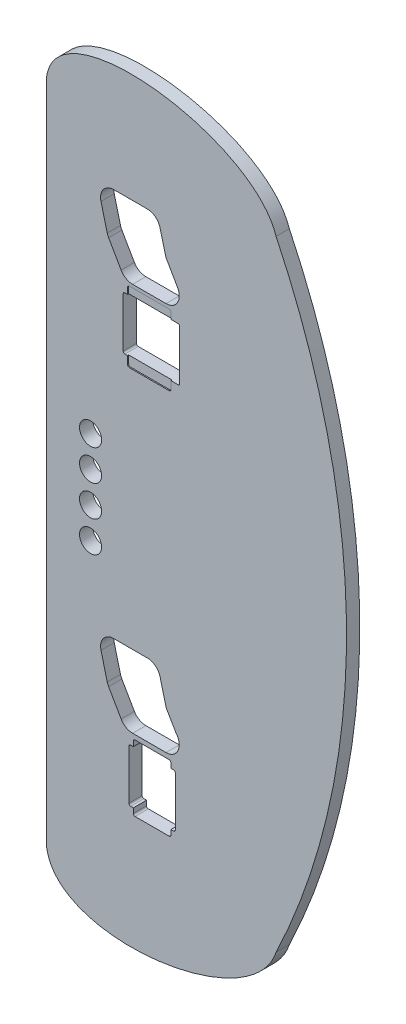
SolidWorks part; units mm, degrees
material "Pine"
ref_plane "Front Plane" through (0, 0, 0) normal (0, 0, 1) x (1, 0, 0)
ref_plane "Top Plane" through (0, 0, 0) normal (0, 1, 0) x (1, 0, 0)
ref_plane "Right Plane" through (0, 0, 0) normal (1, 0, 0) x (0, 0, -1)
sketch "Sketch1" plane through (0, 0, 0) normal (0, 1, 0) x (1, 0, 0)
  line L0 (-92.9216, 89.0184) -> (669.0784, 89.0184)
  line L1 (669.0784, 89.0184) -> (669.0784, 419.2184)
  line L2 (-92.9216, 89.0184) -> (-92.9216, 419.2184)
  line L5 (110.2784, 495.4184) -> (465.8784, 495.4184)
  line L8 (110.2784, 495.4184) -> (-92.9216, 419.2184)
  line L9 (465.8784, 495.4184) -> (669.0784, 419.2184)
  line L10 (-92.9216, 495.4184) -> (669.0784, 495.4184) construction
sketch "Sketch2" plane through (0, 0, 0) normal (0, 0, 1) x (1, 0, 0)
  line L95 (1361.0966, 1819.7347) -> (1361.0966, 996.3635)
  arc A0 (1691.2966, 1027.0491) -> (1691.2966, 1789.0491) centre (733.0004, 1408.0491) ccw
  spline S0 degree 3 poles (1691.2966, 1027.0491) (1656.7077, 922.0591) (1371.3251, 886.2968) (1361.0966, 996.3635) knots 0 0 0 0 7.629784 7.629784 7.629784 7.629784
  spline S1 degree 3 poles (1691.2966, 1789.0491) (1656.7629, 1894.0573) (1371.3251, 1929.8013) (1361.0966, 1819.7347) knots 0 0 0 0 7.638295 7.638295 7.638295 7.638295
sketch "Sketch4" plane through (0, 0, 0) normal (0, 0, 1) x (1, 0, 0)
  line L0 (1439.599, 1277.0692) -> (1448.5991, 1242.0693)
  line L1 (1450.5414, 1237.3053) -> (1468.5414, 1206.0553)
  line L2 (1540.0357, 1097.2035) -> (1540.0357, 1104.1885)
  line L3 (1486.0607, 1185.151) -> (1486.0607, 1006.8697) construction
  line L4 (1486.0607, 1187.3735) -> (1486.0607, 1180.3885)
  line L5 (1540.0357, 1006.8697) -> (1540.0357, 1185.151) construction
  line L6 (1544.7982, 1189.9135) -> (1481.2982, 1189.9135) construction
  line L7 (1488.6007, 1094.6635) -> (1537.4957, 1094.6635)
  line L8 (1482.2507, 1104.1885) -> (1543.8457, 1104.1885)
  line L9 (1546.3857, 1106.7285) -> (1546.3857, 1177.8485)
  line L10 (1543.8457, 1180.3885) -> (1482.2507, 1180.3885)
  line L11 (1479.7107, 1106.7285) -> (1479.7107, 1177.8485)
  line L14 (1550.1957, 1739.1885) -> (1473.9957, 1739.1885)
  line L16 (1471.4557, 1665.5285) -> (1471.4557, 1736.6485)
  line L18 (1473.9957, 1662.9885) -> (1550.1957, 1662.9885)
  line L20 (1540.0357, 1180.3885) -> (1540.0357, 1187.3735)
  line L21 (1486.0607, 1104.1885) -> (1486.0607, 1097.2035)
  line L22 (1540.0357, 1739.1885) -> (1540.0357, 1748.2626)
  line L24 (1485.0488, 1196.5135) -> (1533.0488, 1196.5135)
  line L25 (1550.8991, 1222.2168) -> (1533.383, 1252.007)
  line L26 (1524.4986, 1286.5577) -> (1533.383, 1252.007)
  line L27 (1459.748, 1300.7875) -> (1504.3496, 1300.7875)
  line L28 (1439.599, 1835.8692) -> (1448.5991, 1800.8693)
  line L29 (1450.5414, 1796.1053) -> (1468.5414, 1764.8553)
  line L30 (1485.0488, 1755.3135) -> (1533.0488, 1755.3135)
  line L31 (1549.5562, 1783.8718) -> (1532.852, 1812.8721)
  line L32 (1524.4986, 1845.3577) -> (1532.852, 1812.8721)
  line L33 (1458.0488, 1859.6635) -> (1506.0488, 1859.6635)
  line L34 (1480.3457, 1649.2026) -> (1537.4957, 1649.2026)
  line L35 (1552.7357, 1665.5285) -> (1552.7357, 1736.6485)
  line L36 (1477.8057, 1651.7426) -> (1477.8057, 1662.9885)
  line L37 (1480.3457, 1750.8026) -> (1537.4957, 1750.8026)
  line L38 (1513.0482, 1189.9135) -> (1513.0482, 1196.5135)
  line L39 (1540.0357, 1651.7426) -> (1540.0357, 1748.2626)
  line L40 (1471.4557, 1651.7426) -> (1471.4557, 1748.2626) construction
  line L41 (1477.8057, 1739.1885) -> (1477.8057, 1748.2626)
  line L42 (1477.8057, 1651.7426) -> (1477.8057, 1748.2626) construction
  line L95 (1361.0966, 1948.8635) -> (1361.0966, 996.3635)
  line L115 (1537.4957, 1189.9135) -> (1488.6007, 1189.9135)
  line L202 (1540.0357, 1185.151) -> (1486.0607, 1185.151) construction
  line L203 (1481.2982, 1189.9135) -> (1481.2982, 1006.8697) construction
  line L204 (1544.7982, 1006.8697) -> (1544.7982, 1189.9135) construction
  arc A0 (1691.2966, 1027.0491) -> (1691.2966, 1918.1779) centre (761.2616, 1472.6135) ccw
  arc A1 (1524.4986, 1286.5577) -> (1504.3496, 1300.7875) centre (1506.0488, 1281.8135) ccw
  arc A2 (1479.7107, 1177.8485) -> (1482.2507, 1180.3885) centre (1482.2507, 1177.8485) cw
  arc A3 (1533.0488, 1196.5135) -> (1547.5414, 1227.9274) centre (1533.0488, 1215.5635) ccw
  arc A4 (1448.5991, 1242.0693) -> (1450.5414, 1237.3053) centre (1467.0488, 1246.8135) ccw
  arc A5 (1468.5414, 1206.0553) -> (1485.0488, 1196.5135) centre (1485.0488, 1215.5635) ccw
  arc A6 (1459.748, 1300.7875) -> (1439.599, 1277.0692) centre (1458.0488, 1281.8135) ccw
  circle A7 centre (1513.0482, 1142.2885) radius 12
  arc A8 (1524.4986, 1845.3577) -> (1506.0488, 1859.6635) centre (1506.0488, 1840.6135) ccw
  arc A9 (1546.3857, 1177.8485) -> (1543.8457, 1180.3885) centre (1543.8457, 1177.8485) ccw
  arc A10 (1533.0488, 1755.3135) -> (1549.5562, 1783.8718) centre (1533.0488, 1774.3635) ccw
  arc A11 (1448.5991, 1800.8693) -> (1450.5414, 1796.1053) centre (1467.0488, 1805.6135) ccw
  arc A12 (1543.8457, 1104.1885) -> (1546.3857, 1106.7285) centre (1543.8457, 1106.7285) ccw
  arc A13 (1458.0488, 1859.6635) -> (1439.599, 1835.8692) centre (1458.0488, 1840.6135) ccw
  arc A14 (1482.2507, 1104.1885) -> (1479.7107, 1106.7285) centre (1482.2507, 1106.7285) cw
  arc A15 (1488.6007, 1094.6635) -> (1486.0607, 1097.2035) centre (1488.6007, 1097.2035) cw
  arc A16 (1537.4957, 1094.6635) -> (1540.0357, 1097.2035) centre (1537.4957, 1097.2035) ccw
  arc A17 (1473.9957, 1662.9885) -> (1471.4557, 1665.5285) centre (1473.9957, 1665.5285) cw
  arc A18 (1552.7357, 1665.5285) -> (1550.1957, 1662.9885) centre (1550.1957, 1665.5285) cw
  circle A19 centre (1508.6636, 1700.4221) radius 12
  arc A20 (1468.5414, 1764.8553) -> (1485.0488, 1755.3135) centre (1485.0488, 1774.3635) ccw
  arc A23 (1552.7357, 1736.6485) -> (1550.1957, 1739.1885) centre (1550.1957, 1736.6485) ccw
  arc A26 (1471.4557, 1736.6485) -> (1473.9957, 1739.1885) centre (1473.9957, 1736.6485) cw
  arc A27 (1540.0357, 1187.3735) -> (1537.4957, 1189.9135) centre (1537.4957, 1187.3735) ccw
  arc A28 (1486.0607, 1187.3735) -> (1488.6007, 1189.9135) centre (1488.6007, 1187.3735) cw
  circle A29 centre (1424.5966, 1539.2885) radius 15.875
  circle A30 centre (1424.5966, 1494.8385) radius 15.875
  circle A31 centre (1424.5966, 1450.3885) radius 15.875
  circle A32 centre (1424.5966, 1405.9385) radius 15.875
  arc A33 (1477.8057, 1651.7426) -> (1480.3457, 1649.2026) centre (1480.3457, 1651.7426) ccw
  arc A34 (1537.4957, 1649.2026) -> (1540.0357, 1651.7426) centre (1537.4957, 1651.7426) ccw
  arc A35 (1540.0357, 1748.2626) -> (1537.4957, 1750.8026) centre (1537.4957, 1748.2626) ccw
  arc A36 (1477.8057, 1748.2626) -> (1480.3457, 1750.8026) centre (1480.3457, 1748.2626) cw
  spline S0 degree 3 poles (1691.2966, 1027.0491) (1656.7077, 922.0591) (1371.3251, 886.2968) (1361.0966, 996.3635) knots 0 0 0 0 7.629784 7.629784 7.629784 7.629784
  spline S1 degree 3 poles (1691.2966, 1918.1779) (1656.7629, 2023.1861) (1371.3251, 2058.9302) (1361.0966, 1948.8635) knots 0 0 0 0 7.638295 7.638295 7.638295 7.638295
  dimension "D2" = 2.54
  dimension "D4" = 2.54
  dimension "D5" = 2.54
  dimension "D6" = 2.54
  dimension "D7" = 2.54
  dimension "D8" = 2.54
  dimension "D9" = 2.54
  dimension "D3" = 2.54
  dimension "D15" = 2.54
  dimension "D10" = 2.54
  dimension "D1" = 4.7625
sketch "Sketch5" plane through (0, 0, 0) normal (0, 0, 1) x (1, 0, 0)
  line L0 (1361.0966, 1819.7347) -> (1361.0966, 996.3635)
  line L1 (1361.0966, 1789.0491) -> (1361.0966, 1027.0491)
  line L2 (1540.0357, 1006.8697) -> (1540.0357, 1016.3947)
  line L3 (1486.0607, 1097.3572) -> (1486.0607, 1006.8697) construction
  line L4 (1486.0607, 1102.1197) -> (1486.0607, 1092.5947)
  line L5 (1540.0357, 1006.8697) -> (1540.0357, 1097.3572) construction
  line L6 (1544.7982, 1102.1197) -> (1481.2982, 1102.1197) construction
  line L7 (1486.0607, 1006.8697) -> (1540.0357, 1006.8697)
  line L8 (1479.7107, 1016.3947) -> (1546.3857, 1016.3947)
  line L9 (1546.3857, 1016.3947) -> (1546.3857, 1092.5947)
  line L10 (1546.3857, 1092.5947) -> (1479.7107, 1092.5947)
  line L11 (1479.7107, 1016.3947) -> (1479.7107, 1092.5947)
  line L12 (1540.0357, 1548.8399) -> (1540.0357, 1558.3649)
  line L13 (1486.0607, 1548.8399) -> (1540.0357, 1548.8399)
  line L14 (1546.3857, 1634.5649) -> (1479.7107, 1634.5649)
  line L15 (1486.0607, 1644.0899) -> (1486.0607, 1634.5649)
  line L16 (1479.7107, 1558.3649) -> (1479.7107, 1634.5649)
  line L17 (1540.0357, 1644.0899) -> (1486.0607, 1644.0899)
  line L18 (1479.7107, 1558.3649) -> (1546.3857, 1558.3649)
  line L19 (1546.3857, 1558.3649) -> (1546.3857, 1634.5649)
  line L20 (1540.0357, 1092.5947) -> (1540.0357, 1102.1197)
  line L21 (1486.0607, 1016.3947) -> (1486.0607, 1006.8697)
  line L22 (1540.0357, 1634.5649) -> (1540.0357, 1644.0899)
  line L23 (1486.0607, 1558.3649) -> (1486.0607, 1548.8399)
  line L95 (1361.0966, 1819.7347) -> (1361.0966, 996.3635)
  line L115 (1540.0357, 1102.1197) -> (1486.0607, 1102.1197)
  line L199 (1363.2449, 1823.8418) -> (1361.0966, 1819.7347)
  line L200 (1361.0966, 1819.7347) -> (1361.7967, 1824.3165)
  line L201 (1361.7967, 1824.3165) -> (1363.2449, 1823.8418)
  line L202 (1540.0357, 1097.3572) -> (1486.0607, 1097.3572) construction
  line L203 (1481.2982, 1102.1197) -> (1481.2982, 1006.8697) construction
  line L204 (1544.7982, 1006.8697) -> (1544.7982, 1102.1197) construction
  arc A0 (1691.2966, 1027.0491) -> (1691.2966, 1789.0491) centre (733.0004, 1408.0491) ccw
  circle A1 centre (1506.0488, 1194.0197) radius 15.875
  circle A2 centre (1515.0488, 1159.0198) radius 15.875
  circle A3 centre (1533.0488, 1127.7698) radius 15.875
  circle A4 centre (1467.0488, 1159.0198) radius 15.875
  circle A5 centre (1485.0488, 1127.7698) radius 15.875
  circle A6 centre (1458.0488, 1194.0197) radius 15.875
  circle A7 centre (1513.0482, 1054.4947) radius 12
  circle A8 centre (1506.0488, 1735.9899) radius 15.875
  circle A9 centre (1515.0488, 1700.99) radius 15.875
  circle A10 centre (1533.0488, 1669.74) radius 15.875
  circle A11 centre (1467.0488, 1700.99) radius 15.875
  circle A12 centre (1485.0488, 1669.74) radius 15.875
  circle A13 centre (1458.0488, 1735.9899) radius 15.875
  circle A15 centre (1483.5084, 1375.1967) radius 12
  circle A16 centre (1483.9827, 1438.6917) radius 12
  circle A17 centre (1551.8392, 1408.0266) radius 29.9999
  circle A18 centre (1409.3368, 1408.0266) radius 15.9995
  circle A19 centre (1513.0482, 1596.4649) radius 12
  arc A30 (1539.4945, 1725.9331) -> (1482.0488, 1761.3623) centre (1506.0488, 1735.9899) ccw
  arc A32 (1549.9668, 1700.2938) -> (1539.4945, 1725.9331) centre (1515.0488, 1700.99) ccw
  arc A41 (1509.0488, 1644.3676) -> (1549.9668, 1700.2938) centre (1533.0488, 1669.74) ccw
  arc A46 (1450.1308, 1670.4362) -> (1509.0488, 1644.3676) centre (1485.0488, 1669.74) ccw
  arc A47 (1433.6031, 1711.0467) -> (1450.1308, 1670.4362) centre (1467.0488, 1700.99) ccw
  arc A50 (1482.0488, 1761.3623) -> (1433.6031, 1711.0467) centre (1458.0488, 1735.9899) ccw
  arc A64 (1509.0488, 1102.3974) -> (1549.9668, 1158.3235) centre (1533.0488, 1127.7698) ccw
  arc A66 (1450.1308, 1128.466) -> (1509.0488, 1102.3974) centre (1485.0488, 1127.7698) ccw
  arc A68 (1433.6031, 1169.0765) -> (1450.1308, 1128.466) centre (1467.0488, 1159.0198) ccw
  arc A70 (1539.4945, 1183.9629) -> (1482.0488, 1219.3921) centre (1506.0488, 1194.0197) ccw
  arc A72 (1549.9668, 1158.3235) -> (1539.4945, 1183.9629) centre (1515.0488, 1159.0198) ccw
  arc A73 (1482.0488, 1219.3921) -> (1433.6031, 1169.0765) centre (1458.0488, 1194.0197) ccw
  arc A86 (1474.249, 1382.8299) -> (1489.0021, 1364.5282) centre (1483.5084, 1375.1967) ccw
  arc A89 (1488.8753, 1449.649) -> (1474.6166, 1431.19) centre (1483.9827, 1438.6917) ccw
  arc A97 (1557.861, 1378.6372) -> (1557.0728, 1437.5665) centre (1551.8392, 1408.0266) ccw
  arc A99 (1420.1657, 1419.8299) -> (1400.5179, 1421.402) centre (1409.3362, 1408.0491) ccw
  arc A100 (1402.6554, 1393.5084) -> (1419.641, 1395.8067) centre (1409.3362, 1408.0491) ccw
  spline S0 degree 3 poles (1691.2966, 1027.0491) (1656.7077, 922.0591) (1371.3251, 886.2968) (1361.0966, 996.3635) knots 0 0 0 0 7.629784 7.629784 7.629784 7.629784
  spline S1 degree 3 poles (1691.2966, 1789.0491) (1656.7629, 1894.0573) (1371.3251, 1929.8013) (1361.0966, 1819.7347) knots 0 0 0 0 7.638295 7.638295 7.638295 7.638295
  dimension "D1" = 4.7625
extrude "Boss-Extrude6" add sketch "Sketch4" along normal blind 19.05 contours A0 S1 L95 S0 L33 L22 L14 L18 L20 L10 L9 L8 L2 L7 L21 L11 region at (1560.7515, 1470.6272, 0)
sketch "Sketch8" plane through (0, 0, 0) normal (0, 0, 1) x (1, 0, 0)
  line L2 (1540.0357, 1006.8697) -> (1540.0357, 1016.3947)
  line L3 (1486.0607, 1097.3572) -> (1486.0607, 1006.8697) construction
  line L4 (1486.0607, 1102.1197) -> (1486.0607, 1092.5947)
  line L5 (1540.0357, 1006.8697) -> (1540.0357, 1097.3572) construction
  line L6 (1544.7982, 1102.1197) -> (1481.2982, 1102.1197) construction
  line L7 (1486.0607, 1006.8697) -> (1540.0357, 1006.8697)
  line L8 (1479.7107, 1016.3947) -> (1546.3857, 1016.3947)
  line L9 (1546.3857, 1016.3947) -> (1546.3857, 1092.5947)
  line L10 (1546.3857, 1092.5947) -> (1479.7107, 1092.5947)
  line L11 (1479.7107, 1016.3947) -> (1479.7107, 1092.5947)
  line L12 (1540.0357, 1548.8399) -> (1540.0357, 1558.3649)
  line L13 (1486.0607, 1548.8399) -> (1540.0357, 1548.8399)
  line L14 (1546.3857, 1634.5649) -> (1479.7107, 1634.5649)
  line L15 (1486.0607, 1644.0899) -> (1486.0607, 1634.5649)
  line L16 (1479.7107, 1558.3649) -> (1479.7107, 1634.5649)
  line L17 (1540.0357, 1644.0899) -> (1486.0607, 1644.0899)
  line L18 (1479.7107, 1558.3649) -> (1546.3857, 1558.3649)
  line L19 (1546.3857, 1558.3649) -> (1546.3857, 1634.5649)
  line L20 (1540.0357, 1092.5947) -> (1540.0357, 1102.1197)
  line L21 (1486.0607, 1016.3947) -> (1486.0607, 1006.8697)
  line L22 (1540.0357, 1634.5649) -> (1540.0357, 1644.0899)
  line L23 (1486.0607, 1558.3649) -> (1486.0607, 1548.8399)
  line L95 (1361.0966, 1819.7347) -> (1361.0966, 996.3635)
  line L115 (1540.0357, 1102.1197) -> (1486.0607, 1102.1197)
  line L202 (1540.0357, 1097.3572) -> (1486.0607, 1097.3572) construction
  line L203 (1481.2982, 1102.1197) -> (1481.2982, 1006.8697) construction
  line L204 (1544.7982, 1006.8697) -> (1544.7982, 1102.1197) construction
  arc A0 (1691.2966, 1027.0491) -> (1691.2966, 1789.0491) centre (733.0004, 1408.0491) ccw
  circle A1 centre (1506.0488, 1194.0197) radius 15.875
  circle A2 centre (1515.0488, 1159.0198) radius 15.875
  circle A3 centre (1533.0488, 1127.7698) radius 15.875
  circle A4 centre (1467.0488, 1159.0198) radius 15.875
  circle A5 centre (1485.0488, 1127.7698) radius 15.875
  circle A6 centre (1458.0488, 1194.0197) radius 15.875
  circle A7 centre (1513.0482, 1054.4947) radius 12
  circle A8 centre (1506.0488, 1735.9899) radius 15.875
  circle A9 centre (1515.0488, 1700.99) radius 15.875
  circle A10 centre (1533.0488, 1669.74) radius 15.875
  circle A11 centre (1467.0488, 1700.99) radius 15.875
  circle A12 centre (1485.0488, 1669.74) radius 15.875
  circle A13 centre (1458.0488, 1735.9899) radius 15.875
  circle A15 centre (1483.5084, 1375.1967) radius 12
  circle A16 centre (1483.9827, 1438.6917) radius 12
  circle A17 centre (1551.8392, 1408.0266) radius 29.9999
  circle A18 centre (1409.3368, 1408.0266) radius 15.9995
  circle A19 centre (1513.0482, 1596.4649) radius 12
  arc A30 (1539.4945, 1725.9331) -> (1482.0488, 1761.3623) centre (1506.0488, 1735.9899) ccw
  arc A32 (1549.9668, 1700.2938) -> (1539.4945, 1725.9331) centre (1515.0488, 1700.99) ccw
  arc A41 (1509.0488, 1644.3676) -> (1549.9668, 1700.2938) centre (1533.0488, 1669.74) ccw
  arc A46 (1450.1308, 1670.4362) -> (1509.0488, 1644.3676) centre (1485.0488, 1669.74) ccw
  arc A47 (1433.6031, 1711.0467) -> (1450.1308, 1670.4362) centre (1467.0488, 1700.99) ccw
  arc A50 (1482.0488, 1761.3623) -> (1433.6031, 1711.0467) centre (1458.0488, 1735.9899) ccw
  arc A64 (1509.0488, 1102.3974) -> (1549.9668, 1158.3235) centre (1533.0488, 1127.7698) ccw
  arc A66 (1450.1308, 1128.466) -> (1509.0488, 1102.3974) centre (1485.0488, 1127.7698) ccw
  arc A68 (1433.6031, 1169.0765) -> (1450.1308, 1128.466) centre (1467.0488, 1159.0198) ccw
  arc A70 (1539.4945, 1183.9629) -> (1482.0488, 1219.3921) centre (1506.0488, 1194.0197) ccw
  arc A72 (1549.9668, 1158.3235) -> (1539.4945, 1183.9629) centre (1515.0488, 1159.0198) ccw
  arc A73 (1482.0488, 1219.3921) -> (1433.6031, 1169.0765) centre (1458.0488, 1194.0197) ccw
  arc A86 (1474.249, 1382.8299) -> (1489.0021, 1364.5282) centre (1483.5084, 1375.1967) ccw
  arc A89 (1488.8753, 1449.649) -> (1474.6166, 1431.19) centre (1483.9827, 1438.6917) ccw
  arc A97 (1557.861, 1378.6372) -> (1557.0728, 1437.5665) centre (1551.8392, 1408.0266) ccw
  arc A99 (1420.1657, 1419.8299) -> (1400.5179, 1421.402) centre (1409.3362, 1408.0491) ccw
  arc A100 (1402.6554, 1393.5084) -> (1419.641, 1395.8067) centre (1409.3362, 1408.0491) ccw
  spline S0 degree 3 poles (1691.2966, 1027.0491) (1656.7077, 922.0591) (1371.3251, 886.2968) (1361.0966, 996.3635) knots 0 0 0 0 7.629784 7.629784 7.629784 7.629784
  spline S1 degree 3 poles (1691.2966, 1789.0491) (1656.7629, 1894.0573) (1371.3251, 1929.8013) (1361.0966, 1819.7347) knots 0 0 0 0 7.638295 7.638295 7.638295 7.638295
  dimension "D1" = 4.7625
sketch "Sketch9" plane through (0, 0, 0) normal (0, 0, 1) x (1, 0, 0)
  line L2 (1540.0357, 1006.8697) -> (1540.0357, 1016.3947)
  line L3 (1486.0607, 1097.3572) -> (1486.0607, 1006.8697) construction
  line L4 (1486.0607, 1102.1197) -> (1486.0607, 1092.5947)
  line L5 (1540.0357, 1006.8697) -> (1540.0357, 1097.3572) construction
  line L6 (1544.7982, 1102.1197) -> (1481.2982, 1102.1197) construction
  line L7 (1486.0607, 1006.8697) -> (1540.0357, 1006.8697)
  line L8 (1479.7107, 1016.3947) -> (1546.3857, 1016.3947)
  line L9 (1546.3857, 1016.3947) -> (1546.3857, 1092.5947)
  line L10 (1546.3857, 1092.5947) -> (1479.7107, 1092.5947)
  line L11 (1479.7107, 1016.3947) -> (1479.7107, 1092.5947)
  line L12 (1540.0357, 1548.8399) -> (1540.0357, 1558.3649)
  line L13 (1486.0607, 1548.8399) -> (1540.0357, 1548.8399)
  line L14 (1546.3857, 1634.5649) -> (1479.7107, 1634.5649)
  line L15 (1486.0607, 1644.0899) -> (1486.0607, 1634.5649)
  line L16 (1479.7107, 1558.3649) -> (1479.7107, 1634.5649)
  line L17 (1540.0357, 1644.0899) -> (1486.0607, 1644.0899)
  line L18 (1479.7107, 1558.3649) -> (1546.3857, 1558.3649)
  line L19 (1546.3857, 1558.3649) -> (1546.3857, 1634.5649)
  line L20 (1540.0357, 1092.5947) -> (1540.0357, 1102.1197)
  line L21 (1486.0607, 1016.3947) -> (1486.0607, 1006.8697)
  line L22 (1540.0357, 1634.5649) -> (1540.0357, 1644.0899)
  line L23 (1486.0607, 1558.3649) -> (1486.0607, 1548.8399)
  line L95 (1361.0966, 1819.7347) -> (1361.0966, 996.3635)
  line L115 (1540.0357, 1102.1197) -> (1486.0607, 1102.1197)
  line L202 (1540.0357, 1097.3572) -> (1486.0607, 1097.3572) construction
  line L203 (1481.2982, 1102.1197) -> (1481.2982, 1006.8697) construction
  line L204 (1544.7982, 1006.8697) -> (1544.7982, 1102.1197) construction
  arc A0 (1691.2966, 1027.0491) -> (1691.2966, 1789.0491) centre (733.0004, 1408.0491) ccw
  circle A1 centre (1506.0488, 1194.0197) radius 15.875
  circle A2 centre (1515.0488, 1159.0198) radius 15.875
  circle A3 centre (1533.0488, 1127.7698) radius 15.875
  circle A4 centre (1467.0488, 1159.0198) radius 15.875
  circle A5 centre (1485.0488, 1127.7698) radius 15.875
  circle A6 centre (1458.0488, 1194.0197) radius 15.875
  circle A7 centre (1513.0482, 1054.4947) radius 12
  circle A8 centre (1506.0488, 1735.9899) radius 15.875
  circle A9 centre (1515.0488, 1700.99) radius 15.875
  circle A10 centre (1533.0488, 1669.74) radius 15.875
  circle A11 centre (1467.0488, 1700.99) radius 15.875
  circle A12 centre (1485.0488, 1669.74) radius 15.875
  circle A13 centre (1458.0488, 1735.9899) radius 15.875
  circle A15 centre (1483.5084, 1375.1967) radius 12
  circle A16 centre (1483.9827, 1438.6917) radius 12
  circle A17 centre (1551.8392, 1408.0266) radius 29.9999
  circle A18 centre (1409.3368, 1408.0266) radius 15.9995
  circle A19 centre (1513.0482, 1596.4649) radius 12
  arc A30 (1539.4945, 1725.9331) -> (1482.0488, 1761.3623) centre (1506.0488, 1735.9899) ccw
  arc A32 (1549.9668, 1700.2938) -> (1539.4945, 1725.9331) centre (1515.0488, 1700.99) ccw
  arc A41 (1509.0488, 1644.3676) -> (1549.9668, 1700.2938) centre (1533.0488, 1669.74) ccw
  arc A46 (1450.1308, 1670.4362) -> (1509.0488, 1644.3676) centre (1485.0488, 1669.74) ccw
  arc A47 (1433.6031, 1711.0467) -> (1450.1308, 1670.4362) centre (1467.0488, 1700.99) ccw
  arc A50 (1482.0488, 1761.3623) -> (1433.6031, 1711.0467) centre (1458.0488, 1735.9899) ccw
  arc A64 (1509.0488, 1102.3974) -> (1549.9668, 1158.3235) centre (1533.0488, 1127.7698) ccw
  arc A66 (1450.1308, 1128.466) -> (1509.0488, 1102.3974) centre (1485.0488, 1127.7698) ccw
  arc A68 (1433.6031, 1169.0765) -> (1450.1308, 1128.466) centre (1467.0488, 1159.0198) ccw
  arc A70 (1539.4945, 1183.9629) -> (1482.0488, 1219.3921) centre (1506.0488, 1194.0197) ccw
  arc A72 (1549.9668, 1158.3235) -> (1539.4945, 1183.9629) centre (1515.0488, 1159.0198) ccw
  arc A73 (1482.0488, 1219.3921) -> (1433.6031, 1169.0765) centre (1458.0488, 1194.0197) ccw
  arc A86 (1474.249, 1382.8299) -> (1489.0021, 1364.5282) centre (1483.5084, 1375.1967) ccw
  arc A89 (1488.8753, 1449.649) -> (1474.6166, 1431.19) centre (1483.9827, 1438.6917) ccw
  arc A97 (1557.861, 1378.6372) -> (1557.0728, 1437.5665) centre (1551.8392, 1408.0266) ccw
  arc A99 (1420.1657, 1419.8299) -> (1400.5179, 1421.402) centre (1409.3362, 1408.0491) ccw
  arc A100 (1402.6554, 1393.5084) -> (1419.641, 1395.8067) centre (1409.3362, 1408.0491) ccw
  spline S0 degree 3 poles (1691.2966, 1027.0491) (1656.7077, 922.0591) (1371.3251, 886.2968) (1361.0966, 996.3635) knots 0 0 0 0 7.629784 7.629784 7.629784 7.629784
  spline S1 degree 3 poles (1691.2966, 1789.0491) (1656.7629, 1894.0573) (1371.3251, 1929.8013) (1361.0966, 1819.7347) knots 0 0 0 0 7.638295 7.638295 7.638295 7.638295
  dimension "D1" = 4.7625
sketch "Sketch13" plane through (0, 0, 0) normal (0, 0, 1) x (1, 0, 0)
  line L0 (1439.599, 1277.0692) -> (1448.5991, 1242.0693)
  line L1 (1450.5414, 1237.3053) -> (1468.5414, 1206.0553)
  line L2 (1540.0357, 1097.2035) -> (1540.0357, 1104.1885)
  line L3 (1486.0607, 1185.151) -> (1486.0607, 1006.8697) construction
  line L4 (1486.0607, 1187.3735) -> (1486.0607, 1180.3885)
  line L5 (1540.0357, 1006.8697) -> (1540.0357, 1185.151) construction
  line L6 (1544.7982, 1189.9135) -> (1481.2982, 1189.9135) construction
  line L7 (1488.6007, 1094.6635) -> (1537.4957, 1094.6635)
  line L8 (1482.2507, 1104.1885) -> (1543.8457, 1104.1885)
  line L9 (1546.3857, 1106.7285) -> (1546.3857, 1177.8485)
  line L10 (1543.8457, 1180.3885) -> (1482.2507, 1180.3885)
  line L11 (1479.7107, 1106.7285) -> (1479.7107, 1177.8485)
  line L12 (1540.0357, 1656.0035) -> (1540.0357, 1662.9885)
  line L13 (1488.6007, 1653.4635) -> (1537.4957, 1653.4635)
  line L14 (1543.8457, 1739.1885) -> (1482.2507, 1739.1885)
  line L15 (1486.0607, 1746.1735) -> (1486.0607, 1739.1885)
  line L16 (1479.7107, 1665.5285) -> (1479.7107, 1736.6485)
  line L17 (1537.4957, 1748.7135) -> (1488.6007, 1748.7135)
  line L18 (1482.2507, 1662.9885) -> (1543.8457, 1662.9885)
  line L19 (1546.3857, 1665.5285) -> (1546.3857, 1736.6485)
  line L20 (1540.0357, 1180.3885) -> (1540.0357, 1187.3735)
  line L21 (1486.0607, 1104.1885) -> (1486.0607, 1097.2035)
  line L22 (1540.0357, 1739.1885) -> (1540.0357, 1746.1735)
  line L23 (1486.0607, 1662.9885) -> (1486.0607, 1656.0035)
  line L24 (1485.0488, 1196.5135) -> (1533.0488, 1196.5135)
  line L25 (1550.8991, 1222.2168) -> (1533.383, 1252.007)
  line L26 (1524.4986, 1286.5577) -> (1533.383, 1252.007)
  line L27 (1459.748, 1300.7875) -> (1504.3496, 1300.7875)
  line L28 (1439.599, 1835.8692) -> (1448.5991, 1800.8693)
  line L29 (1450.5414, 1796.1053) -> (1468.5414, 1764.8553)
  line L30 (1485.0488, 1755.3135) -> (1533.0488, 1755.3135)
  line L31 (1549.5562, 1783.8718) -> (1532.852, 1812.8721)
  line L32 (1524.4986, 1845.3577) -> (1532.852, 1812.8721)
  line L33 (1458.0488, 1859.6635) -> (1506.0488, 1859.6635)
  line L34 (1513.0482, 1748.7135) -> (1513.0482, 1755.3135)
  line L38 (1513.0482, 1189.9135) -> (1513.0482, 1196.5135)
  line L95 (1361.0966, 1948.8635) -> (1361.0966, 996.3635)
  line L115 (1537.4957, 1189.9135) -> (1488.6007, 1189.9135)
  line L202 (1540.0357, 1185.151) -> (1486.0607, 1185.151) construction
  line L203 (1481.2982, 1189.9135) -> (1481.2982, 1006.8697) construction
  line L204 (1544.7982, 1006.8697) -> (1544.7982, 1189.9135) construction
  arc A0 (1691.2966, 1027.0491) -> (1691.2966, 1918.1779) centre (761.2616, 1472.6135) ccw
  arc A1 (1524.4986, 1286.5577) -> (1504.3496, 1300.7875) centre (1506.0488, 1281.8135) ccw
  arc A2 (1479.7107, 1177.8485) -> (1482.2507, 1180.3885) centre (1482.2507, 1177.8485) cw
  arc A3 (1533.0488, 1196.5135) -> (1547.5414, 1227.9274) centre (1533.0488, 1215.5635) ccw
  arc A4 (1448.5991, 1242.0693) -> (1450.5414, 1237.3053) centre (1467.0488, 1246.8135) ccw
  arc A5 (1468.5414, 1206.0553) -> (1485.0488, 1196.5135) centre (1485.0488, 1215.5635) ccw
  arc A6 (1459.748, 1300.7875) -> (1439.599, 1277.0692) centre (1458.0488, 1281.8135) ccw
  circle A7 centre (1513.0482, 1142.2885) radius 12
  arc A8 (1524.4986, 1845.3577) -> (1506.0488, 1859.6635) centre (1506.0488, 1840.6135) ccw
  arc A9 (1546.3857, 1177.8485) -> (1543.8457, 1180.3885) centre (1543.8457, 1177.8485) ccw
  arc A10 (1533.0488, 1755.3135) -> (1549.5562, 1783.8718) centre (1533.0488, 1774.3635) ccw
  arc A11 (1448.5991, 1800.8693) -> (1450.5414, 1796.1053) centre (1467.0488, 1805.6135) ccw
  arc A12 (1543.8457, 1104.1885) -> (1546.3857, 1106.7285) centre (1543.8457, 1106.7285) ccw
  arc A13 (1458.0488, 1859.6635) -> (1439.599, 1835.8692) centre (1458.0488, 1840.6135) ccw
  arc A14 (1482.2507, 1104.1885) -> (1479.7107, 1106.7285) centre (1482.2507, 1106.7285) cw
  arc A15 (1488.6007, 1094.6635) -> (1486.0607, 1097.2035) centre (1488.6007, 1097.2035) cw
  arc A16 (1537.4957, 1094.6635) -> (1540.0357, 1097.2035) centre (1537.4957, 1097.2035) ccw
  arc A17 (1479.7107, 1736.6485) -> (1482.2507, 1739.1885) centre (1482.2507, 1736.6485) cw
  arc A18 (1546.3857, 1736.6485) -> (1543.8457, 1739.1885) centre (1543.8457, 1736.6485) ccw
  circle A19 centre (1513.0482, 1701.0885) radius 12
  arc A20 (1468.5414, 1764.8553) -> (1485.0488, 1755.3135) centre (1485.0488, 1774.3635) ccw
  arc A21 (1540.0357, 1746.1735) -> (1537.4957, 1748.7135) centre (1537.4957, 1746.1735) ccw
  arc A22 (1486.0607, 1746.1735) -> (1488.6007, 1748.7135) centre (1488.6007, 1746.1735) cw
  arc A23 (1543.8457, 1662.9885) -> (1546.3857, 1665.5285) centre (1543.8457, 1665.5285) ccw
  arc A24 (1537.4957, 1653.4635) -> (1540.0357, 1656.0035) centre (1537.4957, 1656.0035) ccw
  arc A25 (1488.6007, 1653.4635) -> (1486.0607, 1656.0035) centre (1488.6007, 1656.0035) cw
  arc A26 (1479.7107, 1665.5285) -> (1482.2507, 1662.9885) centre (1482.2507, 1665.5285) ccw
  arc A27 (1540.0357, 1187.3735) -> (1537.4957, 1189.9135) centre (1537.4957, 1187.3735) ccw
  arc A28 (1486.0607, 1187.3735) -> (1488.6007, 1189.9135) centre (1488.6007, 1187.3735) cw
  circle A29 centre (1424.5966, 1539.2885) radius 15.875
  circle A30 centre (1424.5966, 1494.8385) radius 15.875
  circle A31 centre (1424.5966, 1450.3885) radius 15.875
  circle A32 centre (1424.5966, 1405.9385) radius 15.875
  spline S0 degree 3 poles (1691.2966, 1027.0491) (1656.7077, 922.0591) (1371.3251, 886.2968) (1361.0966, 996.3635) knots 0 0 0 0 7.629784 7.629784 7.629784 7.629784
  spline S1 degree 3 poles (1691.2966, 1918.1779) (1656.7629, 2023.1861) (1371.3251, 2058.9302) (1361.0966, 1948.8635) knots 0 0 0 0 7.638295 7.638295 7.638295 7.638295
  dimension "D2" = 2.54
  dimension "D4" = 2.54
  dimension "D5" = 2.54
  dimension "D6" = 2.54
  dimension "D7" = 2.54
  dimension "D8" = 2.54
  dimension "D9" = 2.54
  dimension "D3" = 2.54
  dimension "D15" = 2.54
  dimension "D1" = 4.7625
sketch "Sketch15" plane through (0, 0, 0) normal (0, 0, 1) x (1, 0, 0)
  line L0 (1439.599, 1277.0692) -> (1448.5991, 1242.0693)
  line L1 (1450.5414, 1237.3053) -> (1468.5414, 1206.0553)
  line L2 (1540.0357, 1097.2035) -> (1540.0357, 1104.1885)
  line L3 (1486.0607, 1185.151) -> (1486.0607, 1006.8697) construction
  line L4 (1486.0607, 1187.3735) -> (1486.0607, 1180.3885)
  line L5 (1540.0357, 1006.8697) -> (1540.0357, 1185.151) construction
  line L6 (1544.7982, 1189.9135) -> (1481.2982, 1189.9135) construction
  line L7 (1488.6007, 1094.6635) -> (1537.4957, 1094.6635)
  line L8 (1482.2507, 1104.1885) -> (1543.8457, 1104.1885)
  line L9 (1546.3857, 1106.7285) -> (1546.3857, 1177.8485)
  line L10 (1543.8457, 1180.3885) -> (1482.2507, 1180.3885)
  line L11 (1479.7107, 1106.7285) -> (1479.7107, 1177.8485)
  line L14 (1550.1957, 1739.1885) -> (1473.9957, 1739.1885)
  line L16 (1471.4557, 1665.5285) -> (1471.4557, 1736.6485)
  line L18 (1473.9957, 1662.9885) -> (1550.1957, 1662.9885)
  line L20 (1540.0357, 1180.3885) -> (1540.0357, 1187.3735)
  line L21 (1486.0607, 1104.1885) -> (1486.0607, 1097.2035)
  line L22 (1540.0357, 1739.1885) -> (1540.0357, 1748.2626)
  line L24 (1485.0488, 1196.5135) -> (1533.0488, 1196.5135)
  line L25 (1550.8991, 1222.2168) -> (1533.383, 1252.007)
  line L26 (1524.4986, 1286.5577) -> (1533.383, 1252.007)
  line L27 (1459.748, 1300.7875) -> (1504.3496, 1300.7875)
  line L28 (1439.599, 1835.8692) -> (1448.5991, 1800.8693)
  line L29 (1450.5414, 1796.1053) -> (1468.5414, 1764.8553)
  line L30 (1485.0488, 1755.3135) -> (1533.0488, 1755.3135)
  line L31 (1549.5562, 1783.8718) -> (1532.852, 1812.8721)
  line L32 (1524.4986, 1845.3577) -> (1532.852, 1812.8721)
  line L33 (1458.0488, 1859.6635) -> (1506.0488, 1859.6635)
  line L34 (1480.3457, 1649.2026) -> (1537.4957, 1649.2026)
  line L35 (1552.7357, 1665.5285) -> (1552.7357, 1736.6485)
  line L36 (1477.8057, 1651.7426) -> (1477.8057, 1662.9885)
  line L37 (1480.3457, 1750.8026) -> (1537.4957, 1750.8026)
  line L38 (1513.0482, 1189.9135) -> (1513.0482, 1196.5135)
  line L39 (1540.0357, 1651.7426) -> (1540.0357, 1748.2626)
  line L40 (1471.4557, 1651.7426) -> (1471.4557, 1748.2626) construction
  line L41 (1477.8057, 1739.1885) -> (1477.8057, 1748.2626)
  line L42 (1477.8057, 1651.7426) -> (1477.8057, 1748.2626) construction
  line L95 (1361.0966, 1948.8635) -> (1361.0966, 996.3635)
  line L115 (1537.4957, 1189.9135) -> (1488.6007, 1189.9135)
  line L202 (1540.0357, 1185.151) -> (1486.0607, 1185.151) construction
  line L203 (1481.2982, 1189.9135) -> (1481.2982, 1006.8697) construction
  line L204 (1544.7982, 1006.8697) -> (1544.7982, 1189.9135) construction
  arc A0 (1691.2966, 1027.0491) -> (1691.2966, 1918.1779) centre (761.2616, 1472.6135) ccw
  arc A1 (1524.4986, 1286.5577) -> (1504.3496, 1300.7875) centre (1506.0488, 1281.8135) ccw
  arc A2 (1479.7107, 1177.8485) -> (1482.2507, 1180.3885) centre (1482.2507, 1177.8485) cw
  arc A3 (1533.0488, 1196.5135) -> (1547.5414, 1227.9274) centre (1533.0488, 1215.5635) ccw
  arc A4 (1448.5991, 1242.0693) -> (1450.5414, 1237.3053) centre (1467.0488, 1246.8135) ccw
  arc A5 (1468.5414, 1206.0553) -> (1485.0488, 1196.5135) centre (1485.0488, 1215.5635) ccw
  arc A6 (1459.748, 1300.7875) -> (1439.599, 1277.0692) centre (1458.0488, 1281.8135) ccw
  circle A7 centre (1513.0482, 1142.2885) radius 12
  arc A8 (1524.4986, 1845.3577) -> (1506.0488, 1859.6635) centre (1506.0488, 1840.6135) ccw
  arc A9 (1546.3857, 1177.8485) -> (1543.8457, 1180.3885) centre (1543.8457, 1177.8485) ccw
  arc A10 (1533.0488, 1755.3135) -> (1549.5562, 1783.8718) centre (1533.0488, 1774.3635) ccw
  arc A11 (1448.5991, 1800.8693) -> (1450.5414, 1796.1053) centre (1467.0488, 1805.6135) ccw
  arc A12 (1543.8457, 1104.1885) -> (1546.3857, 1106.7285) centre (1543.8457, 1106.7285) ccw
  arc A13 (1458.0488, 1859.6635) -> (1439.599, 1835.8692) centre (1458.0488, 1840.6135) ccw
  arc A14 (1482.2507, 1104.1885) -> (1479.7107, 1106.7285) centre (1482.2507, 1106.7285) cw
  arc A15 (1488.6007, 1094.6635) -> (1486.0607, 1097.2035) centre (1488.6007, 1097.2035) cw
  arc A16 (1537.4957, 1094.6635) -> (1540.0357, 1097.2035) centre (1537.4957, 1097.2035) ccw
  arc A17 (1473.9957, 1662.9885) -> (1471.4557, 1665.5285) centre (1473.9957, 1665.5285) cw
  arc A18 (1552.7357, 1665.5285) -> (1550.1957, 1662.9885) centre (1550.1957, 1665.5285) cw
  circle A19 centre (1508.6636, 1700.4221) radius 12
  arc A20 (1468.5414, 1764.8553) -> (1485.0488, 1755.3135) centre (1485.0488, 1774.3635) ccw
  arc A23 (1552.7357, 1736.6485) -> (1550.1957, 1739.1885) centre (1550.1957, 1736.6485) ccw
  arc A26 (1471.4557, 1736.6485) -> (1473.9957, 1739.1885) centre (1473.9957, 1736.6485) cw
  arc A27 (1540.0357, 1187.3735) -> (1537.4957, 1189.9135) centre (1537.4957, 1187.3735) ccw
  arc A28 (1486.0607, 1187.3735) -> (1488.6007, 1189.9135) centre (1488.6007, 1187.3735) cw
  circle A29 centre (1424.5966, 1539.2885) radius 15.875
  circle A30 centre (1424.5966, 1494.8385) radius 15.875
  circle A31 centre (1424.5966, 1450.3885) radius 15.875
  circle A32 centre (1424.5966, 1405.9385) radius 15.875
  arc A33 (1477.8057, 1651.7426) -> (1480.3457, 1649.2026) centre (1480.3457, 1651.7426) ccw
  arc A34 (1537.4957, 1649.2026) -> (1540.0357, 1651.7426) centre (1537.4957, 1651.7426) ccw
  arc A35 (1540.0357, 1748.2626) -> (1537.4957, 1750.8026) centre (1537.4957, 1748.2626) ccw
  arc A36 (1477.8057, 1748.2626) -> (1480.3457, 1750.8026) centre (1480.3457, 1748.2626) cw
  spline S0 degree 3 poles (1691.2966, 1027.0491) (1656.7077, 922.0591) (1371.3251, 886.2968) (1361.0966, 996.3635) knots 0 0 0 0 7.629784 7.629784 7.629784 7.629784
  spline S1 degree 3 poles (1691.2966, 1918.1779) (1656.7629, 2023.1861) (1371.3251, 2058.9302) (1361.0966, 1948.8635) knots 0 0 0 0 7.638295 7.638295 7.638295 7.638295
  dimension "D2" = 2.54
  dimension "D4" = 2.54
  dimension "D5" = 2.54
  dimension "D6" = 2.54
  dimension "D7" = 2.54
  dimension "D8" = 2.54
  dimension "D9" = 2.54
  dimension "D3" = 2.54
  dimension "D15" = 2.54
  dimension "D10" = 2.54
  dimension "D1" = 4.7625
extrude "Boss-Extrude7" add sketch "Sketch15" along normal blind 17.4625 contours A36 L41 L14 L22 A35 L37 | L34 A34 L39 L18 L36 A33 region at (1508.9207, 1744.9754, 0) region at (1508.9207, 1656.116, 0)
